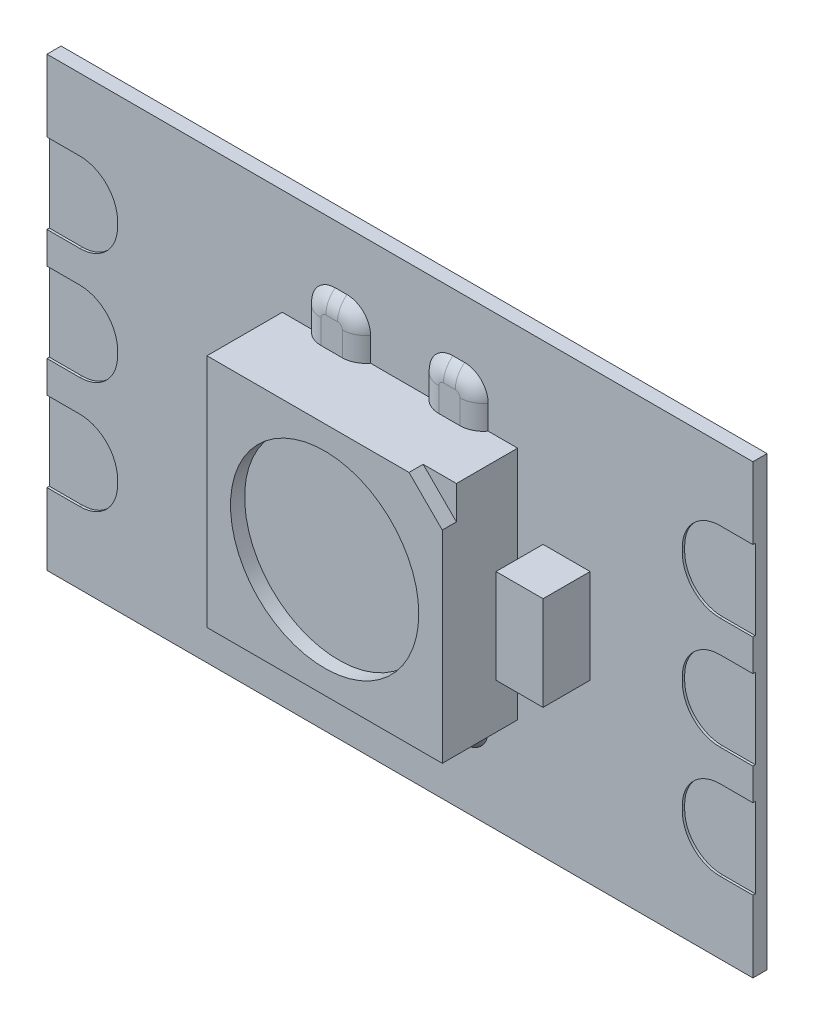
SolidWorks part; units mm, degrees
ref_plane "Plan de face" through (0, 0, 0) normal (0, 0, 1) x (1, 0, 0)
ref_plane "Plan de dessus" through (0, 0, 0) normal (0, 1, 0) x (1, 0, 0)
ref_plane "Plan de droite" through (0, 0, 0) normal (1, 0, 0) x (0, 0, -1)
sketch "Esquisse1" plane through (0, 0, 0) normal (0, 0, 1) x (1, 0, 0)
  line L1 (0, 0) -> (15, 0)
  line L2 (0, 0) -> (0, 9.5)
  line L3 (0, 9.5) -> (15, 9.5)
  line L4 (15, 0) -> (15, 9.5)
  dimension "D1" = 15
  dimension "D2" = 9.5
extrude "Boss.-Extru.1" add sketch "Esquisse1" along normal blind 0.3
sketch "Esquisse2" plane through (0, 0, 0.3) normal (0, 0, 1) x (1, 0, 0)
  line L1 (5, 2.25) -> (10, 2.25)
  line L2 (5, 2.25) -> (5, 7.25)
  line L3 (5, 7.25) -> (10, 7.25)
  line L4 (10, 2.25) -> (10, 7.25)
  line L5 (5, 2.25) -> (10, 7.25) construction
  line L6 (5, 7.25) -> (10, 2.25) construction
  point P0 (7.5, 4.75)
  dimension "D1" = 5
  dimension "D2" = 5
extrude "Boss.-Extru.2" add sketch "Esquisse2" along normal blind 1.6
sketch "Esquisse3" plane through (0, 0, 1.9) normal (0, 0, 1) x (1, 0, 0)
  line L0 (9.2929, 7.25) -> (10, 6.5429)
  line L1 (10, 7.25) -> (5, 7.25) construction
  line L2 (10, 2.25) -> (10, 7.25) construction
  line L3 (10, 6.5429) -> (10, 7.25)
  line L4 (10, 7.25) -> (9.2929, 7.25)
  circle A0 centre (7.5, 4.75) radius 2
  dimension "D1" = 1
  dimension "D2" = 45
extrude "Enlèv. mat.-Extru.1" cut sketch "Esquisse3" against normal blind 0.3
sketch "Esquisse4" plane through (0, 0, 0.3) normal (0, 0, 1) x (1, 0, 0)
  line L0 (7.5, 7.25) -> (7.5, 9.5) construction
  line L1 (10, 7.25) -> (5, 7.25) construction
  line L2 (15, 9.5) -> (0, 9.5) construction
  line L3 (6.25, 7.25) -> (5, 7.25) construction
  line L4 (6.25, 7.25) -> (6.25, 8.8537) construction
  line L5 (6.25, 7.25) -> (7.5, 7.25) construction
  line L6 (8.875, 8.2632) -> (8.625, 8.2632)
  line L7 (5.625, 7.25) -> (6.875, 7.25)
  line L8 (5.625, 7.25) -> (5.625, 7.7632)
  line L9 (6.125, 8.2632) -> (6.375, 8.2632)
  line L10 (6.875, 7.25) -> (6.875, 7.7632)
  line L11 (8.125, 7.25) -> (8.125, 7.7632)
  line L12 (9.375, 7.25) -> (8.125, 7.25)
  line L13 (9.375, 7.25) -> (9.375, 7.7632)
  line L14 (7.5, 4.75) -> (15, 4.75) construction
  line L15 (15, 0) -> (15, 9.5) construction
  line L16 (9.375, 2.25) -> (9.375, 1.7368)
  line L17 (9.375, 2.25) -> (8.125, 2.25)
  line L18 (8.125, 2.25) -> (8.125, 1.7368)
  line L19 (8.875, 1.2368) -> (8.625, 1.2368)
  line L20 (6.125, 1.2368) -> (6.375, 1.2368)
  line L21 (6.875, 2.25) -> (6.875, 1.7368)
  line L22 (5.625, 2.25) -> (6.875, 2.25)
  line L23 (5.625, 2.25) -> (5.625, 1.7368)
  arc A0 (6.375, 8.2632) -> (6.875, 7.7632) centre (6.375, 7.7632) cw
  arc A1 (5.625, 7.7632) -> (6.125, 8.2632) centre (6.125, 7.7632) cw
  arc A2 (8.625, 8.2632) -> (8.125, 7.7632) centre (8.625, 7.7632) ccw
  arc A3 (9.375, 7.7632) -> (8.875, 8.2632) centre (8.875, 7.7632) ccw
  arc A4 (9.375, 1.7368) -> (8.875, 1.2368) centre (8.875, 1.7368) cw
  arc A5 (8.625, 1.2368) -> (8.125, 1.7368) centre (8.625, 1.7368) cw
  arc A6 (6.375, 1.2368) -> (6.875, 1.7368) centre (6.375, 1.7368) ccw
  arc A7 (5.625, 1.7368) -> (6.125, 1.2368) centre (6.125, 1.7368) ccw
  dimension "D1" = 0.5
extrude "Boss.-Extru.3" add sketch "Esquisse4" along normal blind 0.2
fillet "Congé1" radius 0.5 20 edges at (8.125, 1.9934, 0.5) (8.2714, 1.3832, 0.5) (8.75, 1.2368, 0.5) (9.375, 1.9934, 0.5) (5.625, 1.9934, 0.5) (5.7714, 1.3832, 0.5) (6.25, 1.2368, 0.5) (6.875, 1.9934, 0.5) (6.875, 7.5066, 0.5) (5.625, 7.5066, 0.5) (5.7714, 8.1168, 0.5) (6.25, 8.2632, 0.5) (9.375, 7.5066, 0.5) (9.2286, 8.1168, 0.5) (8.75, 8.2632, 0.5) (8.125, 7.5066, 0.5) (9.2286, 1.3832, 0.5) (6.7286, 1.3832, 0.5) (6.7286, 8.1168, 0.5) (8.2714, 8.1168, 0.5)
sketch "Esquisse5" plane through (0, 0, 0.3) normal (0, 0, 1) x (1, 0, 0)
  line L0 (0, 4.75) -> (15, 4.75) construction
  line L1 (0, 9.5) -> (0, 0) construction
  line L2 (15, 0) -> (15, 9.5) construction
  line L3 (0, 9.5) -> (0, 4.75) construction
  line L4 (-1.5, 1.525) -> (0.7, 1.525)
  line L5 (-1.5, 3.9) -> (0.7, 3.9)
  line L6 (-1.5, 3.9) -> (-1.5, 5.6)
  line L7 (-1.5, 5.6) -> (0.7, 5.6)
  line L8 (1.5, 4.7) -> (1.5, 4.8)
  line L9 (-1.5, 3.9) -> (1.5, 5.6) construction
  line L10 (-1.5, 5.6) -> (1.5, 3.9) construction
  line L11 (-1.5, 6.275) -> (0.7, 6.275)
  line L12 (-1.5, 6.275) -> (-1.5, 7.975)
  line L13 (-1.5, 7.975) -> (0.7, 7.975)
  line L14 (1.5, 7.075) -> (1.5, 7.175)
  line L15 (-1.5, 6.275) -> (1.5, 7.975) construction
  line L16 (-1.5, 7.975) -> (1.5, 6.275) construction
  line L17 (1.5, 2.425) -> (1.5, 2.325)
  line L18 (-1.5, 3.225) -> (0.7, 3.225)
  line L19 (-1.5, 3.225) -> (-1.5, 1.525)
  line L20 (7.5, 4.75) -> (7.5, 9.5) construction
  line L21 (15, 9.5) -> (0, 9.5) construction
  line L22 (16.5, 3.225) -> (16.5, 1.525)
  line L23 (16.5, 3.225) -> (14.3, 3.225)
  line L24 (13.5, 2.425) -> (13.5, 2.325)
  line L25 (16.5, 1.525) -> (14.3, 1.525)
  line L26 (16.5, 5.6) -> (14.3, 5.6)
  line L27 (13.5, 4.7) -> (13.5, 4.8)
  line L28 (16.5, 3.9) -> (14.3, 3.9)
  line L29 (16.5, 3.9) -> (16.5, 5.6)
  line L30 (16.5, 7.975) -> (14.3, 7.975)
  line L31 (13.5, 7.075) -> (13.5, 7.175)
  line L32 (16.5, 6.275) -> (14.3, 6.275)
  line L33 (16.5, 6.275) -> (16.5, 7.975)
  arc A0 (14.3, 7.975) -> (13.5, 7.175) centre (14.3, 7.175) ccw
  arc A1 (13.5, 7.075) -> (14.3, 6.275) centre (14.3, 7.075) ccw
  arc A2 (14.3, 5.6) -> (13.5, 4.8) centre (14.3, 4.8) ccw
  arc A3 (13.5, 4.7) -> (14.3, 3.9) centre (14.3, 4.7) ccw
  arc A4 (14.3, 3.225) -> (13.5, 2.425) centre (14.3, 2.425) ccw
  arc A5 (13.5, 2.325) -> (14.3, 1.525) centre (14.3, 2.325) ccw
  arc A6 (0.7, 1.525) -> (1.5, 2.325) centre (0.7, 2.325) ccw
  arc A7 (1.5, 2.425) -> (0.7, 3.225) centre (0.7, 2.425) ccw
  arc A8 (0.7, 3.9) -> (1.5, 4.7) centre (0.7, 4.7) ccw
  arc A9 (0.7, 5.6) -> (1.5, 4.8) centre (0.7, 4.8) cw
  arc A10 (0.7, 6.275) -> (1.5, 7.075) centre (0.7, 7.075) ccw
  arc A11 (0.7, 7.975) -> (1.5, 7.175) centre (0.7, 7.175) cw
  point P12 (0, 7.125)
  point P39 (13.5, 7.975)
  point P42 (13.5, 6.275)
  point P45 (13.5, 5.6)
  point P48 (13.5, 3.9)
  point P51 (13.5, 3.225)
  point P54 (13.5, 1.525)
  point P57 (1.5, 1.525)
  point P60 (1.5, 3.225)
  dimension "D5" = 0.8
  dimension "D1" = 3
  dimension "D2" = 1.7
  dimension "D3" = 1.7
  dimension "D4" = 3
extrude "Enlèv. mat.-Extru.2" cut sketch "Esquisse5" against normal blind 0.05
sketch "Esquisse6" plane through (0, 0, 0.3) normal (0, 0, 1) x (1, 0, 0)
  line L1 (10.5409, 3.75) -> (11.5409, 3.75)
  line L2 (10.5409, 3.75) -> (10.5409, 5.75)
  line L3 (10.5409, 5.75) -> (11.5409, 5.75)
  line L4 (11.5409, 3.75) -> (11.5409, 5.75)
  line L5 (10.5409, 3.75) -> (11.5409, 5.75) construction
  line L6 (10.5409, 5.75) -> (11.5409, 3.75) construction
  point P0 (11.0409, 4.75)
  dimension "D1" = 1
  dimension "D2" = 2
extrude "Boss.-Extru.4" add sketch "Esquisse6" along normal blind 1
sketch "Esquisse7" plane through (0, 0, 0.3) normal (0, 0, 1) x (1, 0, 0)
  line L0 (15, 9.5) -> (0, 9.5) construction
  line L1 (7.5, 9.5) -> (7.5, 0) construction
  line L2 (0, 0) -> (15, 0) construction
sketch "Esquisse8" plane through (0, 7.25, 0) normal (0, 1, 0) x (1, 0, 0)
  line L0 (7.5, -0.3) -> (7.5, -1.9) construction
  line L1 (8.125, -0.3) -> (6.875, -0.3) construction
  line L2 (9.2929, -1.9) -> (5, -1.9) construction
sketch "Esquisse10" plane through (0, 0, 0.3) normal (0, 0, 1) x (1, 0, 0)
  line L0 (-22.3493, 2.9993) -> (37.3493, -56.6993) construction
  circle A0 centre (7.5, -26.85) radius 31.6 construction
